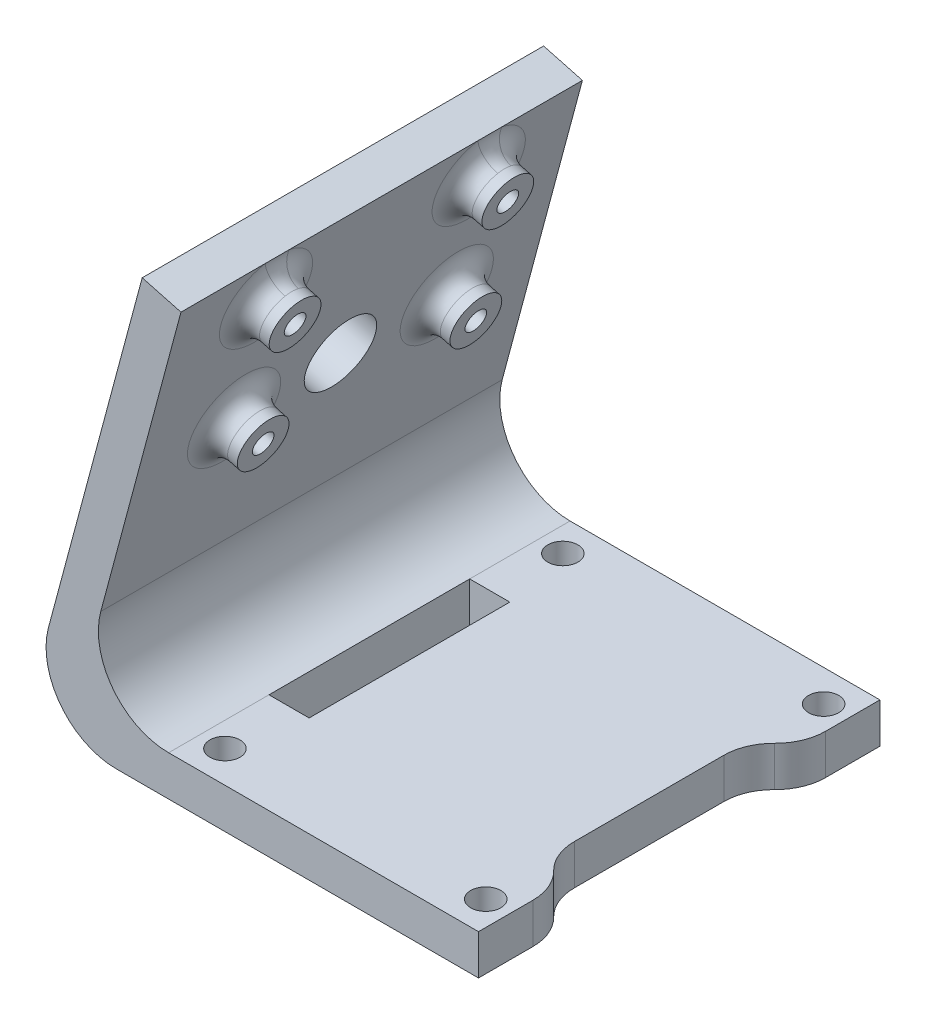
SolidWorks part; units mm, degrees
ref_plane "Piano frontale" through (0, 0, 0) normal (0, 0, 1) x (1, 0, 0)
ref_plane "Piano superiore" through (0, 0, 0) normal (0, 1, 0) x (1, 0, 0)
ref_plane "Piano destro" through (0, 0, 0) normal (1, 0, 0) x (0, 0, -1)
sketch "Schizzo1" plane through (0, 0, 0) normal (0, 0, 1) x (1, 0, 0)
  line L0 (0, 0) -> (-40, 0)
  line L5 (-40, 0) -> (-29.6472, 38.637)
  line L6 (0, -4) -> (-45.2129, -4)
  line L7 (-45.2129, -4) -> (-33.5109, 39.6723)
  line L8 (-33.5109, 39.6723) -> (-29.6472, 38.637)
  line L9 (0, 0) -> (0, -4)
  dimension "D1" = 75
  dimension "D2" = 40
  dimension "D3" = 40
  dimension "D4" = 4
extrude "Estrusione-Estrusione1" add sketch "Schizzo1" along normal blind 40
fillet "Raccordo1" radius 7 2 edges at (-40, 0, 20) (-45.2129, -4, 20)
sketch "Schizzo2" plane through (0, 0, 0) normal (0, 1, 0) x (1, 0, 0)
  line L0 (-30.8774, 0) -> (-30.8774, -40) construction
  line L1 (-30.8774, -10) -> (-26.8774, -10)
  line L2 (-30.8774, -10) -> (-30.8774, -30)
  line L3 (-30.8774, -30) -> (-26.8774, -30)
  line L4 (-26.8774, -10) -> (-26.8774, -30)
  line L5 (0, -40) -> (-30.8774, -40) construction
  dimension "D1" = 20
  dimension "D2" = 10
  dimension "D3" = 4
extrude "Taglio-Estrusione1" cut sketch "Schizzo2" against normal blind 40
sketch "Schizzo3" plane through (-41.1842, 11.0353, 0) normal (-0.9659, 0.2588, 0) x (0, 0, 1)
  line L7 (7.2057, 3.2171) -> (32.4057, 27.2171) construction
  line L8 (7.2057, 27.2171) -> (32.4057, 3.2171) construction
  line L10 (19.8057, 15.2171) -> (19.8057, 27.2171) construction
  line L11 (30.4029, 25.3096) -> (30.4029, 13.0096) construction
  line L12 (30.4029, 25.3096) -> (19.9029, 13.4096) construction
  line L13 (30.4029, 25.3096) -> (9.2086, 25.3096) construction
  circle A1 centre (30.4029, 25.3096) radius 1.05
  circle A2 centre (9.2086, 25.3096) radius 1.05
  circle A3 centre (30.4029, 13.0096) radius 1.05
  circle A4 centre (9.2086, 13.0096) radius 1.05
  circle A6 centre (19.9029, 13.4096) radius 3.5
  point P8 (19.8057, 15.2171)
  point P13 (30.4029, 25.3096)
  point P24 (18.9107, 14.3647)
  dimension "D5" = 2.7659
  dimension "D6" = 2.1
  dimension "D8" = 2.1
  dimension "D11" = 7
  dimension "D1" = 24
  dimension "D2" = 25.2
  dimension "D7" = 12.3
  dimension "D9" = 15.8701
  dimension "D10" = 48.576
extrude "Taglio-Estrusione2" cut sketch "Schizzo3" against normal blind 40
sketch "Schizzo4" plane through (-37.3205, 10, 0) normal (0.9659, -0.2588, 0) x (0, 0, -1)
  circle A0 centre (-9.2086, 13.0096) radius 2.5
  circle A1 centre (-30.4029, 13.0096) radius 2.5
  circle A2 centre (-30.4029, 25.3096) radius 2.5
  circle A3 centre (-9.2086, 25.3096) radius 2.5
  circle A4 centre (-9.2086, 13.0096) radius 1.05
  circle A5 centre (-30.4029, 13.0096) radius 1.05
  circle A6 centre (-30.4029, 25.3096) radius 1.05
  circle A7 centre (-9.2086, 25.3096) radius 1.05
  dimension "D1" = 5
  dimension "D2" = 5
  dimension "D3" = 5
  dimension "D4" = 5
extrude "Estrusione-Estrusione2" add sketch "Schizzo4" along normal blind 3
fillet "Raccordo2" radius 2 4 edges at (-31.417, 32.0324, 30.4029) (-31.417, 32.0324, 9.2086) (-34.6004, 20.1515, 30.4029) (-34.6004, 20.1515, 9.2086)
sketch "Schizzo5" plane through (0, 0, 0) normal (0, 1, 0) x (1, 0, 0)
  line L0 (0, 0) -> (-30.8774, -40) construction
  line L1 (0, -40) -> (-30.8774, 0) construction
  circle A0 centre (-2.4442, -36.8336) radius 1.5
  circle A1 centre (-2.4442, -3.1664) radius 1.5
  circle A2 centre (-28.4332, -3.1664) radius 1.5
  circle A3 centre (-28.4332, -36.8336) radius 1.5
  dimension "D1" = 3
  dimension "D2" = 3
  dimension "D3" = 3
  dimension "D4" = 3
  dimension "D5" = 4
  dimension "D6" = 4
  dimension "D7" = 4
  dimension "D8" = 4
extrude "Taglio-Estrusione3" cut sketch "Schizzo5" against normal blind 17
sketch "Schizzo6" plane through (0, 0, 0) normal (0, 1, 0) x (1, 0, 0)
  line L0 (0, -40) -> (0, 0) construction
  line L1 (0, -20) -> (0, -30)
  line L2 (0, -20) -> (0, -10)
  line L3 (0, -30) -> (-3, -30)
  line L4 (0, -10) -> (-3, -10)
  line L5 (-3, -10) -> (-3, -30)
  dimension "D1" = 10
  dimension "D2" = 10
  dimension "D3" = 3
extrude "Taglio-Estrusione4" cut sketch "Schizzo6" against normal blind 10
fillet "Raccordo3" radius 5 2 edges at (0, -2, 10) (0, -2, 30)
fillet "Raccordo4" radius 5 2 edges at (-3, -2, 10) (-3, -2, 30)
